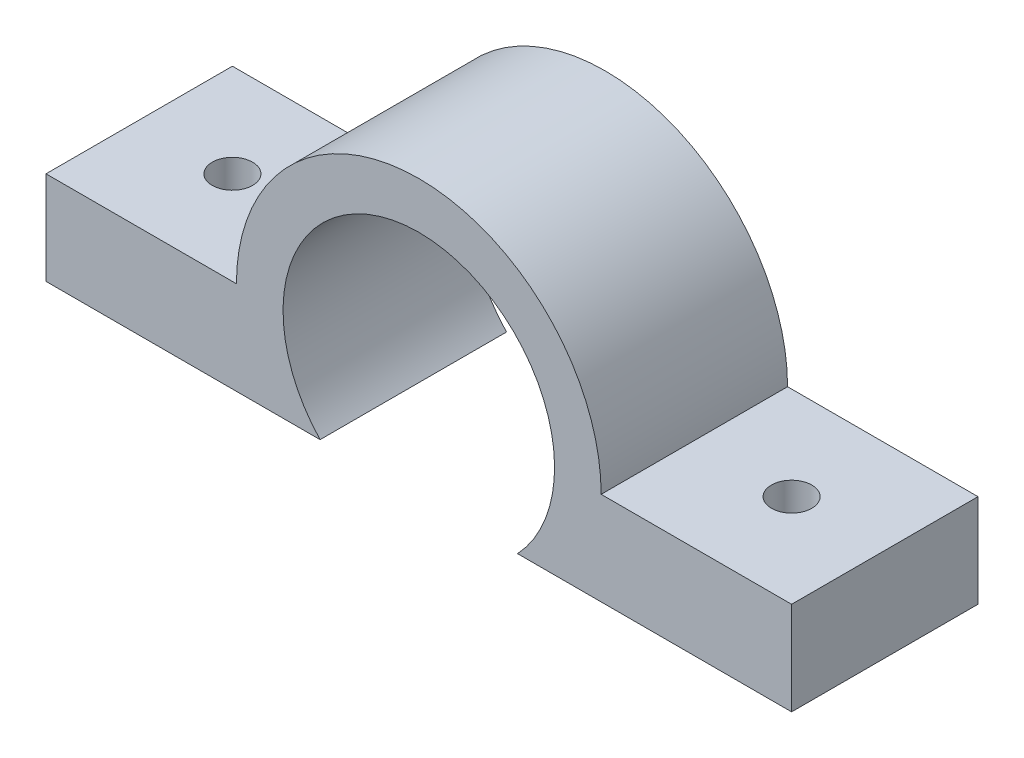
SolidWorks part; units mm, degrees
note: The reader was unsure of these and kept them because the rebuilt part matched: shared geometry of "Sketch1<3>".
material "ABS PC"
ref_plane "Front Plane" through (0, 0, 0) normal (0, 0, 1) x (1, 0, 0)
ref_plane "Top Plane" through (0, 0, 0) normal (0, 1, 0) x (1, 0, 0)
ref_plane "Right Plane" through (0, 0, 0) normal (1, 0, 0) x (0, 0, -1)
sketch "Sketch1" plane through (0, 0, 0) normal (0, 0, 1) x (1, 0, 0)
  line L0 (0, 0) -> (0, 76.2) construction
  line L1 (50.8, -6.35) -> (-50.8, -6.35)
  line L2 (50.8, -6.35) -> (50.8, 6.35)
  line L3 (50.8, 6.35) -> (-50.8, 6.35)
  line L4 (-50.8, -6.35) -> (-50.8, 6.35)
  line L5 (50.8, -6.35) -> (-50.8, 6.35) construction
  line L6 (50.8, 6.35) -> (-50.8, -6.35) construction
  line L8 (-50.8, 6.35) -> (50.8, 6.35) construction
  line L9 (-50.8, 6.35) -> (-50.8, 19.05) construction
  line L10 (-50.8, 19.05) -> (50.8, 19.05) construction
  line L11 (50.8, 6.35) -> (50.8, 19.05) construction
  line L12 (-50.8, 19.05) -> (-50.8, 6.35)
  line L13 (-50.8, 19.05) -> (-24.85, 19.05)
  line L14 (-50.8, 6.35) -> (-13.4521, 6.35)
  line L15 (24.85, 19.05) -> (50.8, 19.05)
  line L16 (50.8, 19.05) -> (50.8, 6.35)
  line L17 (50.8, 6.35) -> (13.4521, 6.35)
  circle A0 centre (0, 19.05) radius 18.5 construction
  circle A1 centre (0, 19.05) radius 24.85 construction
  arc A4 (-13.4521, 6.35) -> (13.4521, 6.35) centre (0, 19.05) ccw
  arc A5 (-24.85, 19.05) -> (24.85, 19.05) centre (0, 19.05) cw
  arc A6 (-13.4521, 6.35) -> (13.4521, 6.35) centre (0, 19.05) cw
  point P0 (0, 0)
  dimension "D4" = 37
  dimension "D6" = 6.35
  dimension "D1" = 101.6
  dimension "D2" = 12.7
  dimension "D3" = 76.2
  dimension "D5" = 19.05
  dimension "D7" = 12.7
extrude "Boss-Extrude1" [suppressed] add sketch "Sketch1" along normal blind 25.4 contours A4 L3 L4 L1 L2
hole_wizard "M5 Clearance Hole1" [suppressed] positions "Sketch2" profile "Sketch3" hole size "M5" standard "ANSI Metric"
sketch "Sketch2" [suppressed] plane through (0, 6.35, 0) normal (0, 1, 0) x (1, 0, 0)
  line L0 (-13.4521, 0) -> (-50.8, 0) construction
  line L1 (-50.8, -25.4) -> (-50.8, 0) construction
  line L2 (50.8, -25.4) -> (50.8, 0) construction
  point P0 (-38.1, -12.7)
  point P2 (38.1, -12.7)
  dimension "D1" = 12.7
  dimension "D2" = 12.7
  dimension "D3" = 12.7
sketch "Sketch3" plane through (-38.1, 6.35, 12.7) normal (1, 0, 0) x (0, 0, 1)
  line L0 (0, 0) -> (0, 12.7)
  line L1 (0, 12.7) -> (2.75, 12.7)
  line L2 (2.75, 12.7) -> (2.75, 0)
  line L5 (2.75, 0) -> (0, 0)
  line L11 (0, -6.35) -> (0, 107.95) construction
  dimension "Thru Hole Dia." = 5.5
  dimension "Thru Hole Depth" = 12.7
extrude "Boss-Extrude2" add sketch "Sketch1<3>" along normal blind 25.4 contours L3 A6 L16 L15 A5 L13 L12
sketch "Sketch1<3>" plane through (0, 0, 0) normal (0, 0, 1) x (1, 0, 0) same geometry as "Sketch1"
hole_wizard "M5 Clearance Hole2" positions "Sketch4" profile "Sketch5" hole size "M5" standard "ANSI Metric" end condition through all
sketch "Sketch4" plane through (0, 19.05, 0) normal (0, 1, 0) x (1, 0, 0)
  line L0 (24.85, -25.4) -> (50.8, -25.4) construction
  line L1 (50.8, -25.4) -> (50.8, 0) construction
  line L2 (-50.8, -25.4) -> (-50.8, 0) construction
  point P0 (38.1, -12.7)
  point P2 (-38.1, -12.7)
  dimension "D1" = 12.7
  dimension "D2" = 12.7
  dimension "D3" = 12.7
sketch "Sketch5" plane through (38.1, 19.05, 12.7) normal (1, 0, 0) x (0, 0, 1)
  line L0 (0, 0) -> (0, 12.7)
  line L1 (0, 12.7) -> (2.75, 12.7)
  line L2 (2.75, 12.7) -> (2.75, 0)
  line L5 (2.75, 0) -> (0, 0)
  line L11 (0, -6.35) -> (0, 107.95) construction
  dimension "Thru Hole Dia." = 5.5
  dimension "Thru Hole Depth" = 12.7
